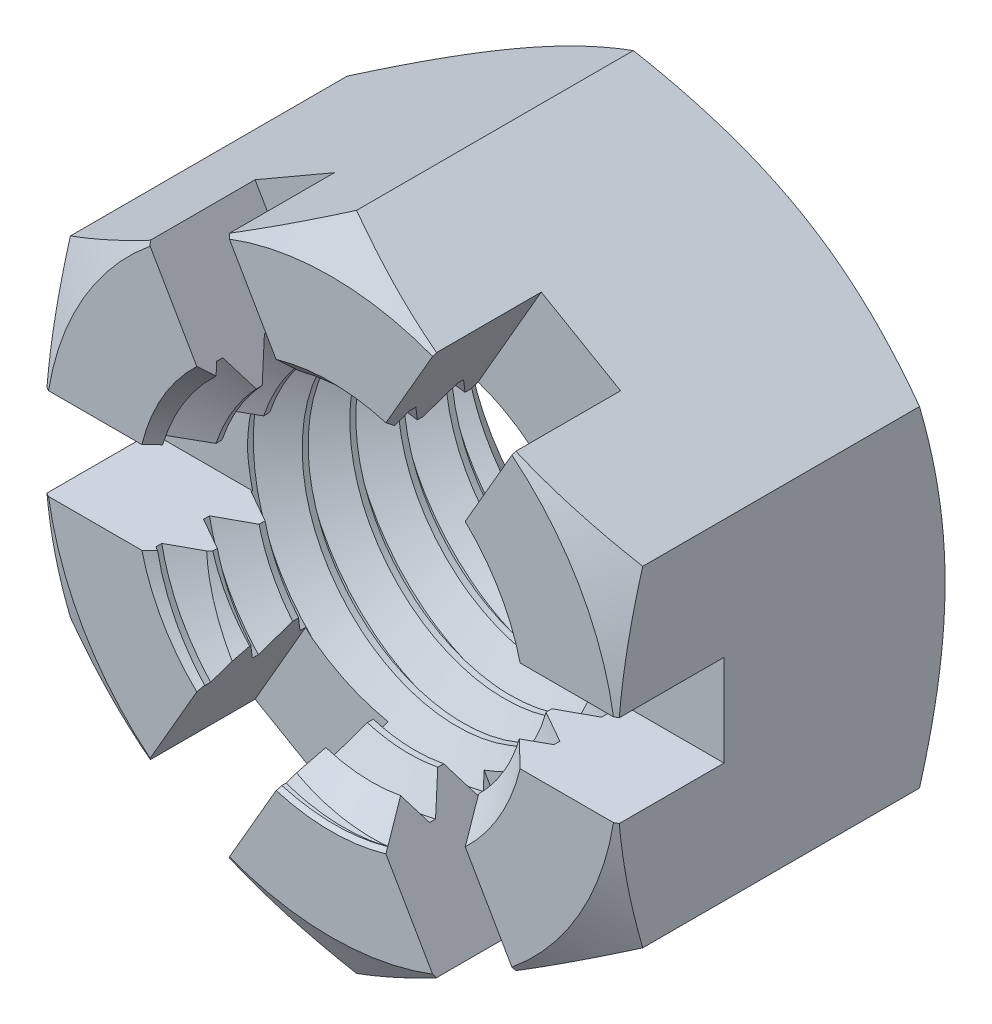
SolidWorks part; units mm, degrees
ref_plane "Front Plane" through (0, 0, 0) normal (0, 0, 1) x (1, 0, 0)
ref_plane "Top Plane" through (0, 0, 0) normal (0, 1, 0) x (1, 0, 0)
ref_plane "Right Plane" through (0, 0, 0) normal (1, 0, 0) x (0, 0, -1)
sketch "Sketch1" plane through (0, 0, 0) normal (0, 0, 1) x (1, 0, 0)
  line L1 (0, 21.997) -> (-19.05, 10.9985)
  line L2 (-19.05, 10.9985) -> (-19.05, -10.9985)
  line L3 (-19.05, -10.9985) -> (0, -21.997)
  line L4 (0, -21.997) -> (19.05, -10.9985)
  line L5 (19.05, -10.9985) -> (19.05, 10.9985)
  line L6 (19.05, 10.9985) -> (0, 21.997)
  circle A0 centre (0, 0) radius 19.05 construction
  dimension "Hex" = 38.1
extrude "Extrude1" add sketch "Sketch1" against normal blind 21.8281
sketch "Sketch2" plane through (0, 0, 0) normal (0, 0, 1) x (1, 0, 0)
  circle A0 centre (0, 0) radius 19.05 construction
  circle A1 centre (0, 0) radius 19.05
extrude "Cut-Extrude1" cut sketch "Sketch2" against normal through all draft 60 flip side to cut
sketch "Sketch3" plane through (0, 0, -21.8281) normal (0, 0, -1) x (-1, 0, 0)
  circle A1 centre (0, 0) radius 19.05
  circle A2 centre (0, 0) radius 19.05
  dimension "D1" = 0
extrude "Cut-Extrude2" cut sketch "Sketch3" against normal through all draft 60 flip side to cut
sketch "Sketch4" plane through (0, 0, 0) normal (0, 0, 1) x (1, 0, 0)
  circle A0 centre (0, 0) radius 12.7
  dimension "Thread Dia" = 25.4
extrude "Cut-Extrude3" cut sketch "Sketch4" against normal through all
sketch "Sketch7" plane through (0, 0, 0) normal (0, 0, 1) x (1, 0, 0)
  circle A4 centre (0, 0) radius 12.954
  circle A5 centre (0, 0) radius 12.954
  dimension "D1" = 0.254
sketch "Sketch8" plane through (0, 0, -21.8281) normal (0, 0, -1) x (-1, 0, 0)
  circle A1 centre (0, 0) radius 12.954
  circle A2 centre (0, 0) radius 12.954 construction
sketch "Sketch5" plane through (0, 0, 0) normal (0, 0, 1) x (1, 0, 0)
  circle A0 centre (0, 0) radius 12.7 construction
  circle A1 centre (0, 0) radius 12.7
curve "Helix/Spiral1" pitch 3.175 height 25.0031 turns 7.875 parameters "pitch"=3.175
sketch "Sketch9" plane through (0, 0, 0) normal (1, 0, 0) x (0, 0, -1)
  line L0 (-1.5875, 12.7) -> (-1.1906, 12.7)
  line L1 (-1.1906, 12.7) -> (0, 10.6378)
  line L2 (-1.5875, 12.7) -> (-2.7781, 10.6378)
  line L3 (-2.7781, 10.6378) -> (0, 10.6378)
  line L4 (-1.3891, 12.7) -> (-1.3891, 10.6378) construction
  line L5 (-2.1828, 11.6689) -> (-0.5953, 11.6689) construction
  line L7 (0, 10.6378) -> (0, 12.7) construction
  line L8 (0, 12.7) -> (0, -12.7) construction
  dimension "D1" = 0.3969
  dimension "D2" = 1.5875
  dimension "D3" = 60
sketch "Sketch12" plane through (0, 0, 0) normal (0, 0, 1) x (1, 0, 0)
  circle A0 centre (0, 0) radius 10.6378
  circle A1 centre (0, 0) radius 12.7 construction
  circle A2 centre (0, 0) radius 12.7
extrude "Extrude2" add sketch "Sketch12" against normal up to surface (21.8281 mm away) up to face at (12.7, 0, -21.8281)
sweep "Cut-Sweep1" cut profiles "Sketch9" path "Helix/Spiral1"
extrude "Cut-Extrude6" cut sketch "Sketch7" against normal through all draft 45
extrude "Cut-Extrude7" cut sketch "Sketch8" against normal through all draft 45
sketch "Sketch13" plane through (0, 0, 0) normal (0, 0, 1) x (1, 0, 0)
  line L0 (-2.6396, 1.524) -> (2.6396, -1.524)
  line L1 (-2.6396, 1.524) -> (6.8854, 18.0218)
  line L2 (2.6396, -1.524) -> (12.1646, 14.9738)
  line L3 (6.8854, 18.0218) -> (12.1646, 14.9738)
  line L4 (19.05, 10.9985) -> (9.525, 16.4978) construction
  dimension "slot width" = 6.096
extrude "Cut-Extrude8" cut sketch "Sketch13" against normal blind 7.112
pattern_circular "CirPattern1" count 6 over 360 about axis through (0, 0, 0) along (0, 0, 1) of "Cut-Extrude8"
equation "\"D2@Sketch9\" = \"pitch@Helix/Spiral1\"*.5"
equation "\"D3@Helix/Spiral1\" = \"pitch@Helix/Spiral1\"+\"Height@Extrude1\""
equation "\"D1@Sketch9\" = \"pitch@Helix/Spiral1\"*.125"
